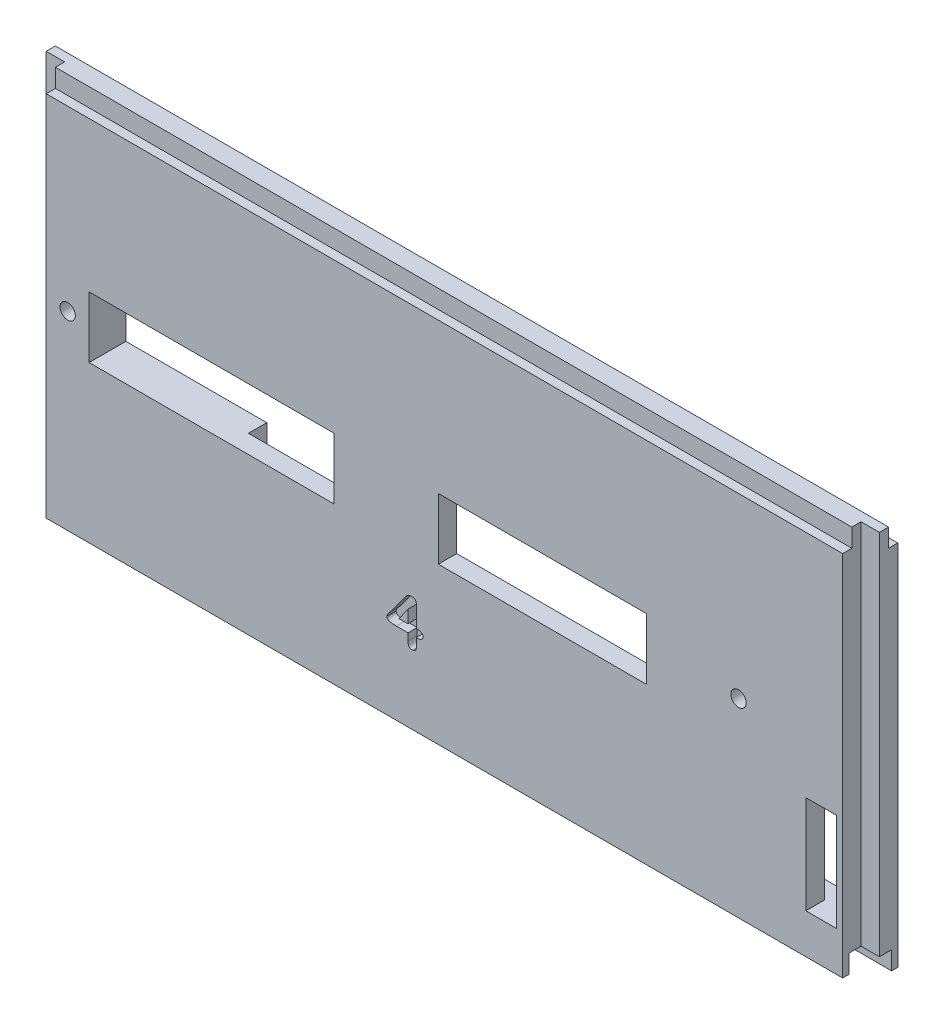
SolidWorks part; units mm, degrees
material "ABS"
ref_plane "前基準面" through (0, 0, 0) normal (0, 0, 1) x (1, 0, 0)
ref_plane "上基準面" through (0, 0, 0) normal (0, 1, 0) x (1, 0, 0)
ref_plane "右基準面" through (0, 0, 0) normal (1, 0, 0) x (0, 0, -1)
sketch "草圖1" plane through (0, 0, 0) normal (0, 0, 1) x (1, 0, 0)
  line L1 (-53.8889, 18.75) -> (76.1111, 18.75)
  line L2 (-53.8889, 18.75) -> (-53.8889, -41.25)
  line L3 (-53.8889, -41.25) -> (76.1111, -41.25)
  line L4 (76.1111, 18.75) -> (76.1111, -41.25)
  dimension "D1" = 60
  dimension "D2" = 130
extrude "填料-伸長1" add sketch "草圖1" along normal blind 6
sketch "草圖2" plane through (-53.8889, 0, 0) normal (-1, 0, 0) x (0, 0, 1)
  line L0 (6, 18.75) -> (0, 18.75) construction
  line L1 (3, 18.75) -> (0, 18.75)
  line L2 (3, 18.75) -> (3, -41.25)
  line L3 (3, -41.25) -> (0, -41.25)
  line L4 (0, 18.75) -> (0, -41.25)
extrude "填料-伸長2" add sketch "草圖2" along normal blind 3 and the other way blind 133
sketch "草圖3" plane through (0, 0, 6) normal (0, 0, 1) x (1, 0, 0)
  line L0 (76.1111, -41.25) -> (76.1111, 18.75) construction
  line L1 (70.1111, -18.75) -> (75.1111, -18.75)
  line L2 (70.1111, -18.75) -> (70.1111, -34.75)
  line L3 (70.1111, -34.75) -> (75.1111, -34.75)
  line L4 (75.1111, -18.75) -> (75.1111, -34.75)
  line L5 (-53.8889, -41.25) -> (76.1111, -41.25) construction
  line L6 (-53.8889, 18.75) -> (-53.8889, -41.25) construction
  line L8 (-46.8889, -5.75) -> (-6.8889, -5.75)
  line L9 (-46.8889, -5.75) -> (-46.8889, -15.75)
  line L10 (-46.8889, -15.75) -> (-6.8889, -15.75)
  line L11 (-6.8889, -5.75) -> (-6.8889, -15.75)
  line L12 (10.1111, -5.75) -> (44.1111, -5.75)
  line L13 (10.1111, -5.75) -> (10.1111, -15.75)
  line L14 (10.1111, -15.75) -> (44.1111, -15.75)
  line L15 (44.1111, -5.75) -> (44.1111, -15.75)
  circle A0 centre (59.1111, -10.25) radius 1.25
  circle A1 centre (-50.3889, -10.25) radius 1.25
  dimension "D5" = 31
  dimension "D6" = 17
  dimension "D7" = 2.5
  dimension "D8" = 3.5
  dimension "D9" = 31
  dimension "D10" = 2.5
  dimension "D1" = 1
  dimension "D2" = 5
  dimension "D3" = 6.5
  dimension "D4" = 16
  dimension "D11" = 7
  dimension "D12" = 40
  dimension "D13" = 4.5
  dimension "D14" = 10
  dimension "D15" = 17
  dimension "D16" = 34
extrude "除料-伸長1" cut sketch "草圖3" against normal blind 6
sketch "草圖4" plane through (0, 0, 6) normal (0, 0, 1) x (1, 0, 0)
  text T0 "4" font "Comic Sans MS" height in points 26
extrude "除料-伸長2" cut sketch "草圖4" against normal blind 1.5
sketch "草圖5" plane through (0, 0, 0) normal (0, 0, -1) x (-1, 0, 0)
  line L1 (-46.1111, 0.2266) -> (23.8889, 0.2266)
  line L2 (-46.1111, 0.2266) -> (-46.1111, -41.25)
  line L3 (-46.1111, -41.25) -> (23.8889, -41.25)
  line L4 (23.8889, 0.2266) -> (23.8889, -41.25)
  line L5 (56.8889, -41.25) -> (-79.1111, -41.25) construction
  line L6 (56.8889, 18.75) -> (56.8889, -41.25) construction
  line L7 (-79.1111, 18.75) -> (-79.1111, -41.25) construction
  line L9 (-70.1111, -18.75) -> (-46.1111, -18.75)
  line L10 (-70.1111, -18.75) -> (-70.1111, -34.75)
  line L11 (-70.1111, -34.75) -> (-46.1111, -34.75)
  line L12 (-46.1111, -18.75) -> (-46.1111, -34.75)
  line M6 (-70.1111, -18.75) -> (-70.1111, -34.75)
  line M9 (-44.1111, -5.75) -> (-10.1111, -5.75)
  line M10 (-10.1111, -5.75) -> (-10.1111, -15.75)
  line M11 (-10.1111, -15.75) -> (-44.1111, -15.75)
  line M12 (-44.1111, -15.75) -> (-44.1111, -5.75)
  line M13 (6.8889, -5.75) -> (46.8889, -5.75)
  line M15 (46.8889, -15.75) -> (6.8889, -15.75)
  line M16 (6.8889, -15.75) -> (6.8889, -5.75)
  line M19 (-79.1111, -41.25) -> (56.8889, -41.25)
  line M21 (56.8889, 18.75) -> (-79.1111, 18.75)
  dimension "D1" = 33
  dimension "D2" = 33
  dimension "D3" = 16
extrude "除料-伸長3" cut sketch "草圖5" against normal blind 3 contours L11 L2 L9 M6 | L4 L2 M21 M19 M15 M16 M13 M12 M9 M10 M11 region at (10.7204, -22.5918, 0) region at (58.1111, -26.75, 0)
chamfer "導角1" distance 3 distance2 15 1 edges at (11.1111, 0.2266, 0) first distance on face at (11.1111, 0.2266, 1.5)
sketch "草圖6" plane through (0, -41.25, 0) normal (0, -1, 0) x (1, 0, 0)
  line L1 (-56.8889, 1) -> (79.1111, 1)
  line L2 (-56.8889, 1) -> (-56.8889, 3)
  line L3 (-56.8889, 3) -> (79.1111, 3)
  line L4 (79.1111, 1) -> (79.1111, 3)
  line L6 (76.1111, 5) -> (-53.8889, 5)
  line L7 (76.1111, 5) -> (76.1111, 3)
  line L8 (76.1111, 3) -> (-53.8889, 3)
  line L9 (-53.8889, 5) -> (-53.8889, 3)
  line L10 (-56.8889, 0) -> (-23.8889, 0) construction
  line M1 (-23.8889, 0) -> (-23.8889, 3)
  line M2 (-23.8889, 3) -> (46.1111, 3)
  line M3 (46.1111, 3) -> (46.1111, 0)
  line M5 (79.1111, 0) -> (79.1111, 3)
  line M6 (79.1111, 3) -> (76.1111, 3)
  line M7 (76.1111, 3) -> (76.1111, 6)
  line M9 (-53.8889, 6) -> (-53.8889, 3)
  line M10 (-53.8889, 3) -> (-56.8889, 3)
  line M11 (-56.8889, 3) -> (-56.8889, 0)
  dimension "D1" = 1
  dimension "D2" = 4
extrude "除料-伸長4" cut sketch "草圖6" against normal blind 3 contours L6 L3 M7 M9 M2 | L3 L1 M10 M11 M1 | L3 L1 M3 M5 M6 region at (-40.3889, -41.25, 2) region at (62.6111, -41.25, 2) region at (11.1111, -41.25, 4)
sketch "草圖7" plane through (0, 18.75, 0) normal (0, 1, 0) x (1, 0, 0)
  line L0 (-56.8889, -3) -> (-56.8889, 0) construction
  line L1 (-56.8889, -1.5) -> (79.1111, -1.5)
  line L2 (-56.8889, -1.5) -> (-56.8889, -3)
  line L3 (-56.8889, -3) -> (79.1111, -3)
  line L4 (79.1111, -1.5) -> (79.1111, -3)
  line L5 (-53.8889, -6) -> (-53.8889, -3) construction
  line L6 (76.1111, -3) -> (-53.8889, -3)
  line L7 (76.1111, -3) -> (76.1111, -4.5)
  line L8 (76.1111, -4.5) -> (-53.8889, -4.5)
  line L9 (-53.8889, -3) -> (-53.8889, -4.5)
  line M1 (76.1111, -6) -> (76.1111, -3)
  line M2 (76.1111, -3) -> (79.1111, -3)
  line M3 (79.1111, -3) -> (79.1111, 0)
  line M5 (-56.8889, 0) -> (-56.8889, -3)
  line M6 (-56.8889, -3) -> (-53.8889, -3)
  line M7 (-53.8889, -3) -> (-53.8889, -6)
extrude "填料-伸長3" add sketch "草圖7" along normal blind 3 contours L3 L1 M6 M2 M3 M5 | L8 L3 M1 M7 region at (11.1111, 18.75, 2.25) region at (11.1111, 18.75, 3.75)
